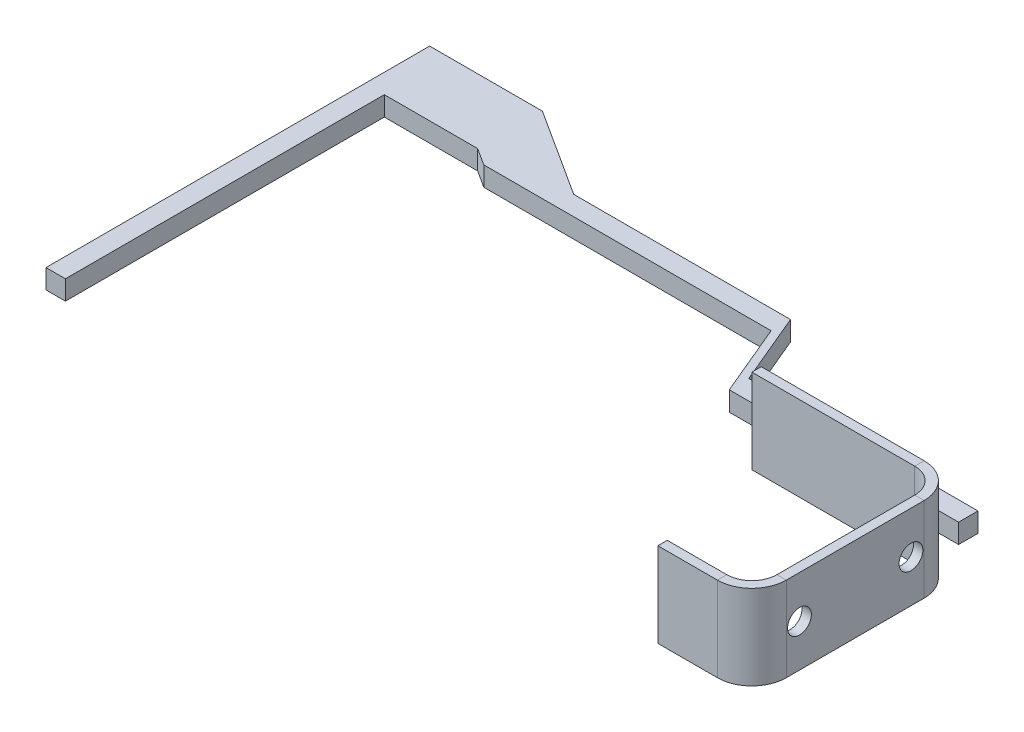
SolidWorks part; units mm, degrees
note: The reader was unsure of these and kept them because the rebuilt part matched: flange length of "Odgięcie krawędzi1", "Odgięcie krawędzi2".
material "Miedź"
ref_plane "Front" through (0, 0, 0) normal (0, 0, 1) x (1, 0, 0)
ref_plane "Top" through (0, 0, 0) normal (0, 1, 0) x (1, 0, 0)
ref_plane "Right" through (0, 0, 0) normal (1, 0, 0) x (0, 0, -1)
sketch "Szkic2" plane through (0, 0, 0) normal (1, 0, 0) x (0, 0, -1)
  line L0 (-13.2667, -0.9913) -> (-13.2667, -7.7413)
  line L1 (-13.2667, -7.7413) -> (3.2333, -7.7413)
  line L2 (3.2333, -7.7413) -> (3.2333, -0.9913)
  line L3 (3.2333, -0.9913) -> (-13.2667, -0.9913)
  dimension "D1" = 16.5
  dimension "D2" = 6.75
base flange "Odgięcie bazowe1" sketch "Szkic2" thickness 0.75 reverse thickness direction no parameters "D1"=0.7366
edge flange "Odgięcie krawędzi1" sketch "Szkic11" flange angle 90 flange length 7.5 flange position material inside bend radius 2 thickness 0.75 relief rectangular parameters "D6"=10
sketch "Szkic11" plane through (-0.75, 0, 13.2667) normal (0, 0, 1) x (0, 1, 0)
  line L0 (-0.9913, 0) -> (-7.7413, 0) construction
  line L1 (-0.9913, 0) -> (-7.7413, 0)
  line L2 (-7.7413, 0) -> (-7.7413, 6.75)
  line L3 (-7.7413, 6.75) -> (-0.9913, 6.75)
  line L4 (-0.9913, 6.75) -> (-0.9913, 0)
bend "Zgięcie krawędziowe1" bend radius 2 bend angle 90 parameters "D5"=1
edge flange "Odgięcie krawędzi2" sketch "Szkic14" flange angle 90 flange length 15.75 flange position material inside bend radius 2 thickness 0.75 relief rectangular parameters "D6"=10
sketch "Szkic14" plane through (-0.75, 0, -3.2333) normal (0, 0, 1) x (0, 1, 0)
  line L1 (-0.9913, 0) -> (-7.7413, 0) construction
  line L2 (-7.7413, 0) -> (-7.7413, 15)
  line L3 (-7.7413, 15) -> (-0.9913, 15)
  line L4 (-0.9913, 15) -> (-0.9913, 0)
  line L5 (-0.9913, 0) -> (-7.7413, 0)
bend "Zgięcie krawędziowe2" bend radius 2 bend angle 90 parameters "D5"=2
sketch "Szkic16" plane through (0, 0, -3.2333) normal (0, 0, -1) x (-1, 0, 0)
  line L0 (18.3, -5.4117) -> (18.3, -3.8617)
  line L2 (0, -7.7413) -> (0, -0.9913) construction
  line L3 (18.3, -3.8617) -> (0, -3.8617)
  line L4 (18.3, -5.4117) -> (0, -5.4117)
  line L5 (0, -5.4117) -> (0, -3.8617)
extrude "Dodanie-wyciągnięcie2" add sketch "Szkic16" along normal blind 1.55
sketch "Szkic18" plane through (0, -3.8617, 0) normal (0, 1, 0) x (1, 0, 0)
  line L0 (-45.0131, 6.2271) -> (-45.0131, 18.3757) construction
  line L1 (-45.0131, 15.0325) -> (-54.0131, 15.0325)
  line L2 (-2.75, -13.2667) -> (-7.5, -13.2667) construction
  line L3 (-54.0131, 15.0325) -> (-54.0131, -15.5857)
  line L4 (-57.5647, 15.0325) -> (-39.661, 15.0325) construction
  line L5 (-38.0131, 10.5325) -> (-45.0131, 15.0325)
  line L6 (-54.0131, -15.5857) -> (-52.4631, -15.5857)
  line L8 (-52.4631, -15.5857) -> (-52.4631, 9.8643)
  line L9 (-15.6131, 2.9143) -> (-15.6131, 6.9143) construction
  line L10 (-52.4631, 9.8643) -> (-45.0131, 9.8643)
  line L11 (-20.7131, 2.9143) -> (-20.7131, 9.6883) construction
  line L12 (-18.3, 4.7833) -> (-18.3, 3.2333)
  line L13 (-18.3, 4.7833) -> (-20.7131, 10.5325)
  line L14 (-20.7131, 10.5325) -> (-38.0131, 10.5325)
  line L15 (0, 4.7833) -> (0, 3.2333) construction
  line L16 (-18.3, 3.2333) -> (-15.75, 3.2333) construction
  line L17 (-18.3, 4.7833) -> (-18.3, 3.2333) construction
  line L18 (-18.3, 3.2333) -> (-20.7131, 8.9825)
  line L19 (-20.7131, 8.9825) -> (-43.6414, 8.9825)
  line L20 (-43.6414, 8.9825) -> (-45.0131, 9.8643)
  point P7 (-5.125, -13.2667)
  point P21 (0, 4.0083)
  dimension "D1" = 31.2263
  dimension "D2" = 5.1
  dimension "D3" = 17.3
  dimension "D4" = 7
  dimension "D5" = 4.5
  dimension "D6" = 28.2991
extrude "Dodanie-wyciągnięcie3" add sketch "Szkic18" against normal blind 1.55
sketch "Szkic19" plane through (0, 0, 0) normal (1, 0, 0) x (0, 0, -1)
  line L0 (4.8818, -4.3663) -> (-19.8191, -4.3663) construction
  line L2 (-5.0167, -7.7413) -> (-5.0167, 4.0182) construction
  line L3 (-10.5167, -7.7413) -> (0.4833, -7.7413) construction
  circle A0 centre (-5.0167, -4.3663) radius 4.45 construction
  circle A1 centre (-0.5667, -4.3663) radius 0.95
  circle A2 centre (-9.4644, -4.3663) radius 0.95
  dimension "D1" = 1.9
  dimension "D2" = 1.9
  dimension "D3" = 8.8977
extrude "Wytnij-wyciągnięcie1" cut sketch "Szkic19" against normal up to surface (0.75 mm away) normal cut yes up to face at (-0.75, -4.3663, 5.0167)
sketch "Linie zgięcia1" [suppressed] plane through (0, 0, 0) normal (0, 1, 0) x (1, 0, 0)
sketch "Ramka-graniczna1" [suppressed] plane through (0, 0, 0) normal (0, 1, 0) x (1, 0, 0)
sheet metal parameters "Arkusz blachy2" thickness 0.75 parameters "D1"=0.7366
flat pattern "Rozłożony model2" [suppressed]
sketch "Linie zgięcia2" plane through (0, 0, 0) normal (0, 1, 0) x (1, 0, 0)
sketch3d "Ramka-graniczna2" [suppressed]
  line L0 (16.8848, -8.0117, 0) -> (-4.2152, -8.0117, 0) construction
  line L1 (16.8848, -1.2617, 0) -> (-4.2152, -1.2617, 0) construction
  line L2 (16.8848, -8.0117, 0) -> (16.8848, -1.2617, 0) construction
  line L3 (-4.2152, -8.0117, 0) -> (-4.2152, -1.2617, 0) construction
sheet metal parameters "Arkusz blachy3" thickness 0.75 parameters "D1"=0.7366
flat pattern "Rozłożony model2"
sketch "Linie zgięcia2" plane through (0, 0, 0) normal (1, 0, 0) x (0, 0, -1)
  line L0 (-16.0002, -1.2617) -> (-16.0002, -8.0117) construction
  line L1 (-16.0002, -1.2617) -> (-16.0002, -8.0117) construction
sketch3d "Ramka-graniczna2" [suppressed]
  line L0 (-22.6155, -8.0117, 0) -> (4.2152, -8.0117, 0) construction
  line L1 (-22.6155, -1.2617, 0) -> (4.2152, -1.2617, 0) construction
  line L2 (-22.6155, -8.0117, 0) -> (-22.6155, -1.2617, 0) construction
  line L3 (4.2152, -8.0117, 0) -> (4.2152, -1.2617, 0) construction
bend of the flat pattern "Rozłożone-<Zgięcie krawędziowe1>1"
sheet metal parameters "Arkusz blachy4" thickness 0.75 parameters "D1"=0.7366
flat pattern "Rozłożony model2"
sketch "Linie zgięcia2" plane through (0, 0, 0) normal (1, 0, 0) x (0, 0, -1)
  line L0 (-16.0002, -1.2617) -> (-16.0002, -8.0117) construction
  line L1 (-16.0002, -1.2617) -> (-16.0002, -8.0117) construction
  line L2 (3.2305, -8.0117) -> (3.2305, -1.2617) construction
  line L3 (3.2305, -8.0117) -> (3.2305, -1.2617) construction
sketch3d "Ramka-graniczna2" [suppressed]
  line L0 (-22.6155, -8.0117, 0) -> (18.0958, -8.0117, 0) construction
  line L1 (-22.6155, -1.2617, 0) -> (18.0958, -1.2617, 0) construction
  line L2 (-22.6155, -8.0117, 0) -> (-22.6155, -1.2617, 0) construction
  line L3 (18.0958, -8.0117, 0) -> (18.0958, -1.2617, 0) construction
bend of the flat pattern "Rozłożone-<Zgięcie krawędziowe1>1"
bend of the flat pattern "Rozłożone-<Zgięcie krawędziowe2>1"
sheet metal parameters "Arkusz blachy6" thickness 0.75 parameters "D1"=0.7366
flat pattern "Rozłożony model2"
sketch "Linie zgięcia2" plane through (0, 0, 0) normal (1, 0, 0) x (0, 0, -1)
  line L0 (-16.0002, -1.2617) -> (-16.0002, -8.0117) construction
  line L1 (-16.0002, -1.2617) -> (-16.0002, -8.0117) construction
  line L2 (3.2305, -8.0117) -> (3.2305, -1.2617) construction
  line L3 (3.2305, -8.0117) -> (3.2305, -1.2617) construction
sketch3d "Ramka-graniczna2" [suppressed]
  line L0 (-22.6155, -8.0117, 0) -> (18.0958, -8.0117, 0) construction
  line L1 (-22.6155, -1.2617, 0) -> (18.0958, -1.2617, 0) construction
  line L2 (-22.6155, -8.0117, 0) -> (-22.6155, -1.2617, 0) construction
  line L3 (18.0958, -8.0117, 0) -> (18.0958, -1.2617, 0) construction
bend of the flat pattern "Rozłożone-<Zgięcie krawędziowe1>1"
bend of the flat pattern "Rozłożone-<Zgięcie krawędziowe2>1"
sheet metal parameters "Arkusz blachy7" thickness 0.75 parameters "D1"=0.7366
flat pattern "Rozłożony model2"
sketch "Linie zgięcia2" plane through (0, 0, 0) normal (1, 0, 0) x (0, 0, -1)
  line L0 (-12.382, -0.9913) -> (-12.382, -7.7413) construction
  line L1 (-12.382, -0.9913) -> (-12.382, -7.7413) construction
  line L2 (2.3487, -7.7413) -> (2.3487, -0.9913) construction
  line L3 (2.3487, -7.7413) -> (2.3487, -0.9913) construction
sketch3d "Ramka-graniczna2" [suppressed]
  line L0 (-18.9973, -7.7413, 0) -> (17.214, -7.7413, 0) construction
  line L1 (-18.9973, -0.9913, 0) -> (17.214, -0.9913, 0) construction
  line L2 (-18.9973, -7.7413, 0) -> (-18.9973, -0.9913, 0) construction
  line L3 (17.214, -7.7413, 0) -> (17.214, -0.9913, 0) construction
bend of the flat pattern "Rozłożone-<Zgięcie krawędziowe1>1"
bend of the flat pattern "Rozłożone-<Zgięcie krawędziowe2>1"
sheet metal parameters "Arkusz blachy8" thickness 0.75 parameters "D1"=0.7366
flat pattern "Rozłożony model2"
sketch "Linie zgięcia2" plane through (0, 0, 0) normal (1, 0, 0) x (0, 0, -1)
  line L0 (-12.382, -0.9913) -> (-12.382, -7.7413) construction
  line L1 (-12.382, -0.9913) -> (-12.382, -7.7413) construction
  line L2 (2.3487, -7.7413) -> (2.3487, -0.9913) construction
  line L3 (2.3487, -7.7413) -> (2.3487, -0.9913) construction
sketch3d "Ramka-graniczna2" [suppressed]
  line L0 (-18.9973, -7.7413, 0) -> (17.214, -7.7413, 0) construction
  line L1 (-18.9973, -0.9913, 0) -> (17.214, -0.9913, 0) construction
  line L2 (-18.9973, -7.7413, 0) -> (-18.9973, -0.9913, 0) construction
  line L3 (17.214, -7.7413, 0) -> (17.214, -0.9913, 0) construction
bend of the flat pattern "Rozłożone-<Zgięcie krawędziowe1>1"
bend of the flat pattern "Rozłożone-<Zgięcie krawędziowe2>1"
